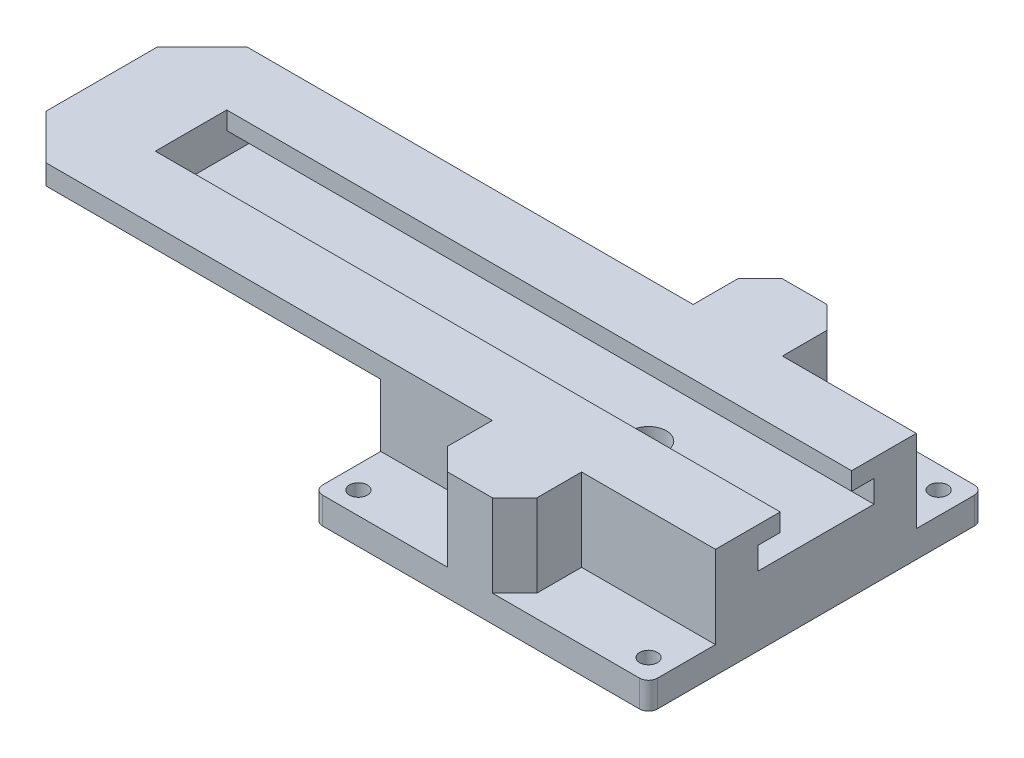
SolidWorks part; units mm, degrees
ref_plane "Front Plane" through (0, 0, 0) normal (0, 0, 1) x (1, 0, 0)
ref_plane "Top Plane" through (0, 0, 0) normal (0, 1, 0) x (1, 0, 0)
ref_plane "Right Plane" through (0, 0, 0) normal (1, 0, 0) x (0, 0, -1)
sketch "Sketch1" plane through (0, 0, 0) normal (0, 1, 0) x (1, 0, 0)
  line L2 (80, -16) -> (220, -16)
  line L3 (220, -16) -> (220, -45.5)
  line L4 (220, -45.5) -> (60, -45.5)
  line L7 (220, 29.5) -> (220, 0)
  line L8 (80, -16) -> (80, 0)
  line L9 (80, 0) -> (220, 0)
  line L10 (220, 29.5) -> (60, 29.5)
  line L11 (60, 29.5) -> (60, -45.5)
  point P2 (80, -8)
  point P9 (0, 0)
  point P10 (0, 0)
  point P11 (0, 0)
  point P12 (0, 0)
  point P13 (0, 0)
  dimension "D1" = 16
  dimension "D2" = 29.5
  dimension "D3" = 29.5
  dimension "D4" = 160
  dimension "D5" = 140
  dimension "D6" = 160
extrude "Boss-Extrude1" add sketch "Sketch1" along normal blind 4
sketch "Sketch2" plane through (0, 0, 0) normal (0, 1, 0) x (1, 0, 0)
  line L0 (209.7303, -8) -> (-59.5425, -8) construction
  line L1 (220, -8) -> (220, 5) construction
  line L4 (220, 5) -> (220, 29.5)
  line L5 (220, 29.5) -> (60, 29.5)
  line L6 (60, 29.5) -> (60, -45.5)
  line L7 (60, 29.5) -> (60, -45.5) construction
  line L8 (220, -21) -> (220, -45.5)
  line L10 (220, -45.5) -> (60, -45.5)
  line L11 (220, 5) -> (80, 5)
  line L12 (80, 5) -> (80, -21)
  line L13 (80, -21) -> (220, -21)
  point P18 (0, -8)
  point P19 (60, -8)
  dimension "D1" = 13
extrude "Boss-Extrude2" add sketch "Sketch2" against normal blind 5
sketch "Sketch3" plane through (0, 0, 0) normal (0, 1, 0) x (1, 0, 0)
  line L0 (60, 29.5) -> (220, 29.5)
  line L1 (220, 29.5) -> (220, -45.5)
  line L2 (220, -45.5) -> (60, -45.5)
  line L3 (60, -45.5) -> (60, 29.5)
extrude "Boss-Extrude3" add sketch "Sketch3" against normal blind 5.5 from offset 5 offset against normal yes
sketch "Sketch4" plane through (0, 0, 0) normal (0, 1, 0) x (1, 0, 0)
  line L6 (60, -8) -> (145, -8) construction
  line L7 (60, -45.5) -> (60, 29.5) construction
  line L8 (145, -8) -> (145, -45.5)
  line L9 (145, -45.5) -> (220, -45.5)
  line L10 (220, -45.5) -> (220, 29.5)
  line L11 (220, 29.5) -> (145, 29.5)
  line L12 (145, 29.5) -> (145, -8)
  line L13 (60, -8) -> (60, 29.5) construction
  dimension "D1" = 85
  dimension "D2" = 37.5
  dimension "D3" = 75
  dimension "D4" = 75
  dimension "D5" = 75
  dimension "D6" = 37.5
extrude "Boss-Extrude4" add sketch "Sketch4" against normal blind 10 from offset 10.5 contours L9 L10 L11 L12 L8 offset against normal yes
sketch "Sketch17" plane through (0, 0, 0) normal (0, 1, 0) x (1, 0, 0)
  line L0 (220, -8) -> (182.5, -8) construction
  line L2 (220, 29.5) -> (220, -45.5) construction
  circle A1 centre (182.5, -8) radius 15
  dimension "D2" = 30
  dimension "D1" = 37.5
extrude "Boss-Extrude7" add sketch "Sketch17" against normal blind 8 from offset 20.5 offset against normal yes
sketch "Sketch5" plane through (0, 0, 0) normal (0, 1, 0) x (1, 0, 0)
  line L0 (180, -45.5) -> (180, 29.5) construction
  line L3 (145, -45.5) -> (220, -45.5) construction
  line L6 (220, 29.5) -> (145, 29.5) construction
  line L9 (145, -8) -> (220, -8) construction
  line L10 (145, 29.5) -> (145, -45.5) construction
  line L11 (220, -45.5) -> (220, 29.5) construction
  circle A1 centre (182.5, -8) radius 10.5
  dimension "D1" = 21
extrude "Cut-Extrude1" cut sketch "Sketch5" against normal blind 12 from offset 25 offset against normal yes
sketch "Sketch7" plane through (0, 0, 0) normal (0, 1, 0) x (1, 0, 0)
  circle A1 centre (182.5, -8) radius 1.5
  dimension "D1" = 3
extrude "Cut-Extrude2" cut sketch "Sketch7" against normal blind 25 from offset 4 offset against normal yes
sketch "Sketch8" plane through (0, 0, 0) normal (0, 1, 0) x (1, 0, 0)
  circle A1 centre (182.5, -8) radius 4
  dimension "D1" = 8
extrude "Cut-Extrude3" cut sketch "Sketch8" against normal blind 18.5 from offset 5 offset against normal yes
sketch "Sketch18" plane through (0, 0, 0) normal (0, 1, 0) x (1, 0, 0)
  line L0 (60, 29.5) -> (170, 29.5)
  line L1 (60, 29.5) -> (220, 29.5) construction
  line L2 (170, 29.5) -> (170, 14.5)
  line L3 (170, 14.5) -> (60, 14.5)
  line L4 (60, -45.5) -> (60, 29.5) construction
  line L5 (60, 14.5) -> (60, 29.5)
  line L6 (60, -8) -> (220, -8) construction
  line L8 (170, -45.5) -> (170, -30.5)
  line L9 (60, -45.5) -> (170, -45.5)
  line L10 (60, -30.5) -> (60, -45.5)
  line L11 (170, -30.5) -> (60, -30.5)
  line L12 (220, 29.5) -> (220, 14.5)
  line L13 (220, 29.5) -> (220, -45.5) construction
  line L14 (220, 14.5) -> (190, 14.5)
  line L15 (190, 14.5) -> (190, 29.5)
  line L16 (190, 29.5) -> (220, 29.5)
  line L17 (220, -45.5) -> (220, -30.5)
  line L18 (220, -30.5) -> (190, -30.5)
  line L19 (190, -45.5) -> (220, -45.5)
  line L20 (190, -30.5) -> (190, -45.5)
  dimension "D1" = 110
  dimension "D2" = 15
  dimension "D3" = 30
  dimension "D4" = 15
extrude "Cut-Extrude5" cut sketch "Sketch18" against normal blind 18.5 from offset 4
sketch "Sketch9" plane through (0, 0, 0) normal (0, 1, 0) x (1, 0, 0)
  line L0 (182.5, -8) -> (150, -8) construction
  line L2 (150, -8) -> (150, -40.5) construction
  line L8 (182.5, -8) -> (182.5, -66.9205) construction
  circle A6 centre (150, -40.5) radius 2
  circle A7 centre (150, 24.5) radius 2
  circle A8 centre (215, 24.5) radius 2
  circle A9 centre (215, -40.5) radius 2
  dimension "D1" = 32.5
  dimension "D2" = 32.5
  dimension "D3" = 4
extrude "Cut-Extrude6" cut sketch "Sketch9" against normal blind 40 from offset 4
chamfer "Chamfer1" distance 10 angle 45 5 edges at (102.5, -10.5, 30.5) (60, -3.25, 30.5) (60, -10.5, 8) (60, -3.25, -14.5) (102.5, -10.5, -14.5)
fillet "Fillet1" radius 2 4 edges at (220, -17.5, 45.5) (145, -17.5, 45.5) (220, -17.5, -29.5) (145, -17.5, -29.5)
chamfer "Chamfer2" distance 5 angle 45 4 edges at (190, -5.25, 45.5) (170, -5.25, 45.5) (170, -5.25, -29.5) (190, -5.25, -29.5)
